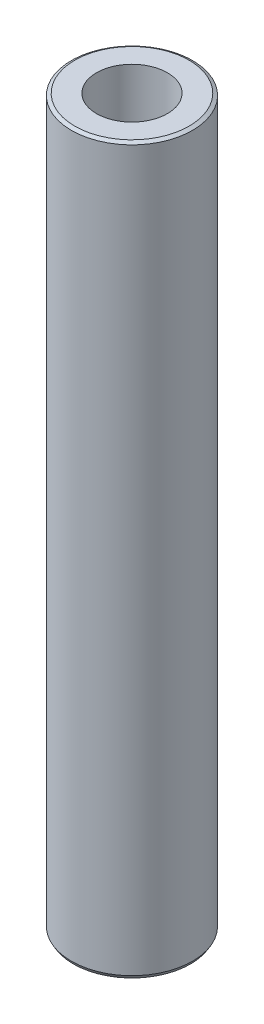
SolidWorks part; units mm, degrees
ref_plane "Front Plane" through (0, 0, 0) normal (0, 0, 1) x (1, 0, 0)
ref_plane "Top Plane" through (0, 0, 0) normal (0, 1, 0) x (1, 0, 0)
ref_plane "Right Plane" through (0, 0, 0) normal (1, 0, 0) x (0, 0, -1)
sketch "Sketch1" plane through (0, 0, 0) normal (0, 1, 0) x (1, 0, 0)
  circle A0 centre (0, 0) radius 7.5
  dimension "SHAFT_OD" = 15
extrude "Boss-Extrude1" add sketch "Sketch1" along normal blind 89.7762
sketch "Sketch2" plane through (0, 0, 0) normal (0, 1, 0) x (1, 0, 0)
  circle A0 centre (0, 0) radius 4.39
  dimension "BORE_D" = 8.7801
extrude "Cut-Extrude1" cut sketch "Sketch2" along normal through all
chamfer "Chamfer1" distance 0.2428 angle 60 2 edges at (0, 89.7762, 7.5) (0, 0, 7.5) first distance on face at (0, 89.7762, 7.5) first distance on face at (0, 0, 4.39)
